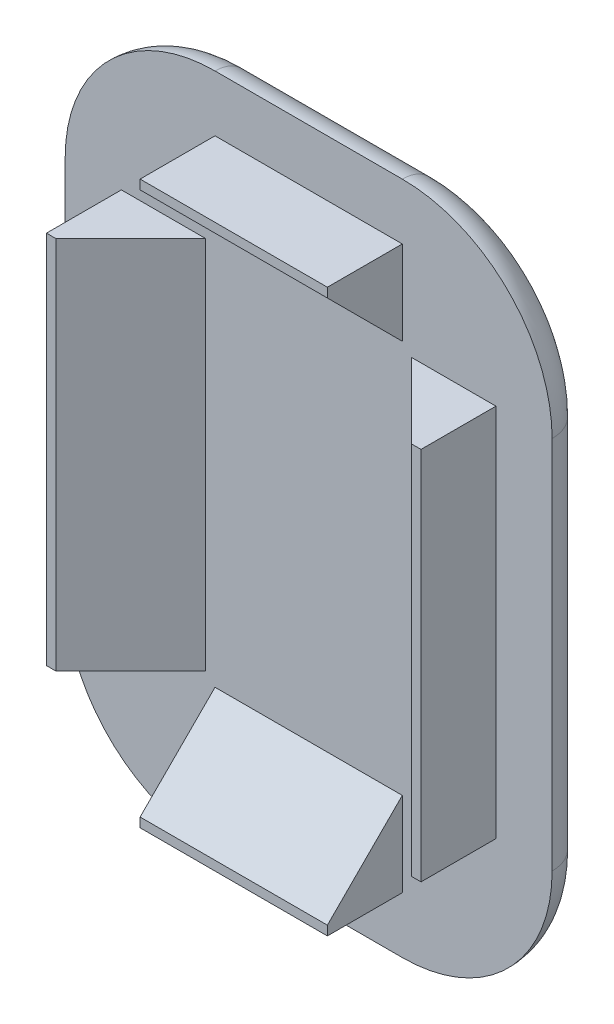
SolidWorks part; units mm, degrees
ref_plane "Спереди" through (0, 0, 0) normal (0, 0, 1) x (1, 0, 0)
ref_plane "Сверху" through (0, 0, 0) normal (0, 1, 0) x (1, 0, 0)
ref_plane "Справа" through (0, 0, 0) normal (1, 0, 0) x (0, 0, -1)
sketch "Эскиз1" plane through (0, 0, 0) normal (0, 0, 1) x (1, 0, 0)
  line L0 (-25.8092, -31.534) -> (-22.5747, -31.534) construction
  line L1 (-30.8092, -26.534) -> (-30.8092, -18.5653) construction
  line L2 (-25.8092, -1.534) -> (-22.5747, -1.534) construction
  line L3 (-10.8092, -26.534) -> (-10.8092, -18.5653) construction
  line L4 (-19.0869, -31.534) -> (-15.8092, -31.534) construction
  line L7 (-10.8092, -14.5032) -> (-10.8092, -6.534) construction
  line L21 (-30.8092, -14.5032) -> (-30.8092, -6.534) construction
  line L23 (-19.0869, -1.534) -> (-15.8092, -1.534) construction
  line L24 (-10.8092, -18.5653) -> (-10.8092, -14.5032) construction
  line L25 (-19.0869, -1.534) -> (-22.5747, -1.534) construction
  line L26 (-30.8092, -18.5653) -> (-30.8092, -14.5032) construction
  line L27 (-22.5747, -31.534) -> (-19.0869, -31.534) construction
  line L28 (-25.8092, -34.534) -> (-22.5747, -34.534)
  line L29 (-22.5747, -34.534) -> (-19.0869, -34.534)
  line L30 (-19.0869, -34.534) -> (-15.8092, -34.534)
  line L31 (-7.8092, -26.534) -> (-7.8092, -18.5653)
  line L32 (-7.8092, -18.5653) -> (-7.8092, -14.5032)
  line L33 (-7.8092, -14.5032) -> (-7.8092, -6.534)
  line L34 (-19.0869, 1.466) -> (-15.8092, 1.466)
  line L35 (-19.0869, 1.466) -> (-22.5747, 1.466)
  line L36 (-25.8092, 1.466) -> (-22.5747, 1.466)
  line L37 (-33.8092, -14.5032) -> (-33.8092, -6.534)
  line L38 (-33.8092, -18.5653) -> (-33.8092, -14.5032)
  line L39 (-33.8092, -26.534) -> (-33.8092, -18.5653)
  line L40 (-25.8092, -31.034) -> (-22.5747, -31.034) construction
  line L41 (-22.5747, -31.034) -> (-19.0869, -31.034) construction
  line L42 (-19.0869, -31.034) -> (-15.8092, -31.034) construction
  line L43 (-11.3092, -26.534) -> (-11.3092, -18.5653) construction
  line L44 (-11.3092, -18.5653) -> (-11.3092, -14.5032) construction
  line L45 (-11.3092, -14.5032) -> (-11.3092, -6.534) construction
  line L46 (-19.0869, -2.034) -> (-15.8092, -2.034) construction
  line L47 (-19.0869, -2.034) -> (-22.5747, -2.034) construction
  line L48 (-25.8092, -2.034) -> (-22.5747, -2.034) construction
  line L49 (-30.3092, -14.5032) -> (-30.3092, -6.534) construction
  line L50 (-30.3092, -18.5653) -> (-30.3092, -14.5032) construction
  line L51 (-30.3092, -26.534) -> (-30.3092, -18.5653) construction
  arc A0 (-15.8092, -31.534) -> (-10.8092, -26.534) centre (-15.8092, -26.534) ccw construction
  arc A1 (-25.8092, -31.534) -> (-30.8092, -26.534) centre (-25.8092, -26.534) cw construction
  arc A2 (-30.8092, -6.534) -> (-25.8092, -1.534) centre (-25.8092, -6.534) cw construction
  arc A3 (-15.8092, -1.534) -> (-10.8092, -6.534) centre (-15.8092, -6.534) cw construction
  arc A8 (-15.8092, -34.534) -> (-7.8092, -26.534) centre (-15.8092, -26.534) ccw
  arc A9 (-15.8092, 1.466) -> (-7.8092, -6.534) centre (-15.8092, -6.534) cw
  arc A10 (-33.8092, -6.534) -> (-25.8092, 1.466) centre (-25.8092, -6.534) cw
  arc A11 (-25.8092, -34.534) -> (-33.8092, -26.534) centre (-25.8092, -26.534) cw
  arc A12 (-15.8092, -31.034) -> (-11.3092, -26.534) centre (-15.8092, -26.534) ccw construction
  arc A13 (-15.8092, -2.034) -> (-11.3092, -6.534) centre (-15.8092, -6.534) cw construction
  arc A14 (-30.3092, -6.534) -> (-25.8092, -2.034) centre (-25.8092, -6.534) cw construction
  arc A15 (-25.8092, -31.034) -> (-30.3092, -26.534) centre (-25.8092, -26.534) cw construction
  dimension "D1" = 5
  dimension "D2" = 20
  dimension "D3" = 3
  dimension "D4" = 0.5
extrude "Бобышка-Вытянуть1" add sketch "Эскиз1" along normal blind 2
sketch "Эскиз2" plane through (0, 0, 2) normal (0, 0, 1) x (1, 0, 0)
  line L0 (-30.3092, -26.534) -> (-30.8092, -26.534)
  line L1 (-30.8092, -26.534) -> (-30.8092, -6.534)
  line L2 (-30.8092, -6.534) -> (-30.3092, -6.534)
  line L3 (-30.3092, -6.534) -> (-30.3092, -26.534)
  line L4 (-25.8092, -31.034) -> (-15.8092, -31.034)
  line L5 (-15.8092, -31.034) -> (-15.8092, -31.534)
  line L6 (-15.8092, -31.534) -> (-25.8092, -31.534)
  line L7 (-25.8092, -31.534) -> (-25.8092, -31.034)
  line L8 (-11.3092, -26.534) -> (-10.8092, -26.534)
  line L9 (-10.8092, -26.534) -> (-10.8092, -6.534)
  line L10 (-10.8092, -6.534) -> (-11.3092, -6.534)
  line L11 (-11.3092, -6.534) -> (-11.3092, -26.534)
  line L12 (-15.8092, -2.034) -> (-15.8092, -1.534)
  line L13 (-15.8092, -1.534) -> (-25.8092, -1.534)
  line L14 (-25.8092, -1.534) -> (-25.8092, -2.034)
  line L15 (-25.8092, -2.034) -> (-15.8092, -2.034)
extrude "Бобышка-Вытянуть2" add sketch "Эскиз2" along normal blind 4
chamfer "Фаска1" distance 4 angle 45 4 edges at (-20.8092, -31.034, 2) (-30.3092, -16.534, 2) (-20.8092, -2.034, 2) (-11.3092, -16.534, 2)
fillet "Скругление1" radius 2 8 edges at (-31.4661, -0.8771, 0) (-20.8092, 1.466, 0) (-10.1524, -0.8771, 0) (-7.8092, -16.534, 0) (-10.1524, -32.1908, 0) (-20.8092, -34.534, 0) (-31.4661, -32.1908, 0) (-33.8092, -16.534, 0)
